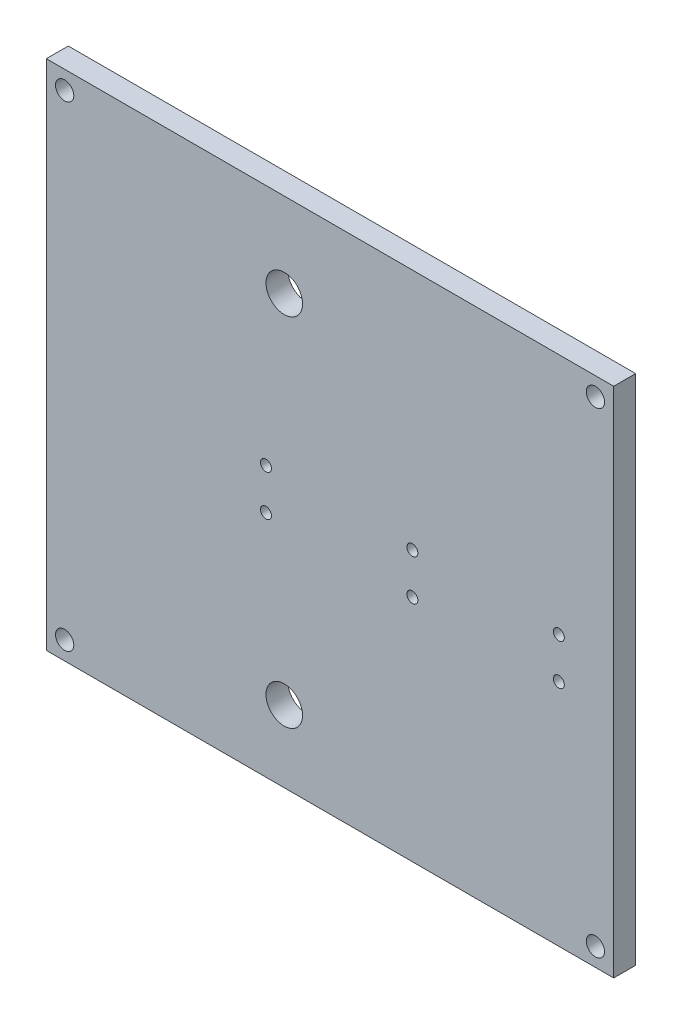
SolidWorks part; units mm, degrees
ref_plane "Plan de face" through (0, 0, 0) normal (0, 0, 1) x (1, 0, 0)
ref_plane "Plan de dessus" through (0, 0, 0) normal (0, 1, 0) x (1, 0, 0)
ref_plane "Plan de droite" through (0, 0, 0) normal (1, 0, 0) x (0, 0, -1)
sketch "Esquisse1" plane through (0, 0, 0) normal (0, 0, 1) x (1, 0, 0)
  line L1 (-77.5, 75.5) -> (77.5, 75.5)
  line L2 (-77.5, 75.5) -> (-77.5, -64.5)
  line L3 (-77.5, -64.5) -> (77.5, -64.5)
  line L4 (77.5, 75.5) -> (77.5, -64.5)
  line L5 (0, 131.3497) -> (0, -131.3497) construction
  circle A0 centre (-12.5, -44.9) radius 5
  circle A1 centre (-12.5, 52.46) radius 5
  circle A2 centre (-72.5, -59.5) radius 2.5
  circle A3 centre (-72.5, 70.5) radius 2.5
  circle A4 centre (72.5, -59.5) radius 2.5
  circle A5 centre (72.5, 70.5) radius 2.5
  point P21 (77.5, 57.8493)
  dimension "D3" = 10
  dimension "D8" = 5
  dimension "D12" = 10
  dimension "D17" = 5
  dimension "D1" = 140
  dimension "D2" = 155
  dimension "D4" = 65
  dimension "D5" = 19.6
  dimension "D6" = 77.5
  dimension "D7" = 23.04
  dimension "D9" = 5
  dimension "D10" = 5
  dimension "D11" = 65
  dimension "D13" = 5
  dimension "D14" = 5
  dimension "D15" = 5
  dimension "D16" = 5
  dimension "D18" = 5
extrude "Boss.-Extru.1" add sketch "Esquisse1" along normal blind 6
sketch "Esquisse6" plane through (0, 0, 6) normal (0, 0, 1) x (1, 0, 0)
  line L0 (77.5, -64.5) -> (77.5, 75.5) construction
  line L1 (79.9353, 9.26) -> (-27.4347, 9.26) construction
  line L2 (-27.4347, -1.9) -> (97.1192, -1.9) construction
  circle A0 centre (-17.5, 9.26) radius 1.5
  circle A1 centre (22.5, 9.26) radius 1.5
  circle A2 centre (62.5, 9.26) radius 1.5
  circle A3 centre (62.5, -1.9) radius 1.5
  circle A4 centre (22.5, -1.9) radius 1.5
  circle A5 centre (-17.5, -1.9) radius 1.5
  circle A6 centre (-12.5, 52.46) radius 5 construction
  circle A7 centre (-12.5, -44.9) radius 5 construction
  dimension "D1" = 3
  dimension "D2" = 3
  dimension "D3" = 3
  dimension "D4" = 3
  dimension "D5" = 3
  dimension "D6" = 3
  dimension "D7" = 40
  dimension "D9" = 15
  dimension "D12" = 15
  dimension "D8" = 40
  dimension "D10" = 40
  dimension "D11" = 40
  dimension "D13" = 43.2
  dimension "D14" = 43
extrude "Enlèv. mat.-Extru.1" cut sketch "Esquisse6" against normal blind 6
